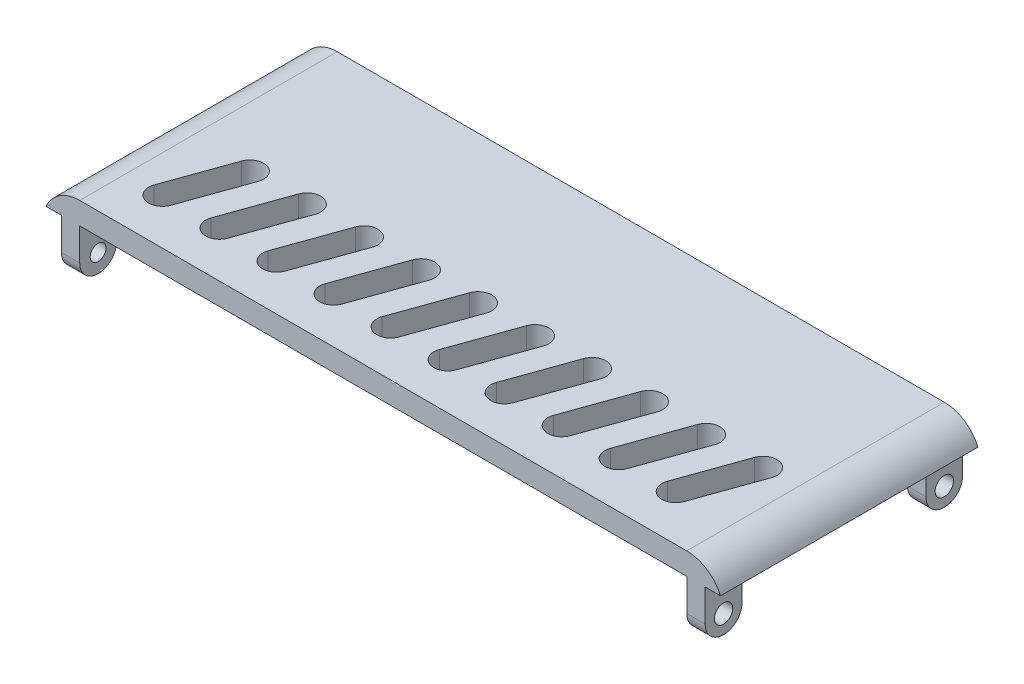
SolidWorks part; units mm, degrees
ref_plane "前视基准面" through (0, 0, 0) normal (0, 0, 1) x (1, 0, 0)
ref_plane "上视基准面" through (0, 0, 0) normal (0, 1, 0) x (1, 0, 0)
ref_plane "右视基准面" through (0, 0, 0) normal (1, 0, 0) x (0, 0, -1)
sketch "草图2" plane through (0, 0, 0) normal (0, 1, 0) x (1, 0, 0)
  line L1 (-31.0872, 15.1404) -> (42.9128, 15.1404)
  line L2 (-31.0872, 15.1404) -> (-31.0872, -12.8596)
  line L3 (-31.0872, -12.8596) -> (42.9128, -12.8596)
  line L4 (42.9128, 15.1404) -> (42.9128, -12.8596)
  dimension "D1" = 74
  dimension "D2" = 28
extrude "凸台-拉伸1" add sketch "草图2" along normal blind 4
fillet "圆角1" radius 4 2 edges at (-31.0872, 4, -1.1404) (42.9128, 4, -1.1404)
sketch "草图3" plane through (0, 0, -15.1404) normal (0, 0, -1) x (-1, 0, 0)
  line L1 (31.0872, 0) -> (-42.9128, 0)
  line L2 (31.0872, 0) -> (31.0872, 1.6)
  line L3 (31.0872, 1.6) -> (-42.9128, 1.6)
  line L4 (-42.9128, 0) -> (-42.9128, 1.6)
  dimension "D1" = 1.6
extrude "切除-拉伸1" cut sketch "草图3" against normal through all
sketch "草图15" plane through (0, 1.6, 0) normal (0, -1, 0) x (1, 0, 0)
  line L0 (33.5789, 9.0596) -> (41.4128, 9.0596)
  line L2 (45.2135, 5.0596) -> (45.2135, 10.0596)
  line L3 (45.2135, 10.0596) -> (33.5789, 10.0596)
  line L4 (33.5789, 9.0596) -> (33.5789, 10.0596)
  line L5 (42.5789, -15.1404) -> (42.5789, 12.8596) construction
  line L6 (41.4128, 9.0596) -> (41.4128, 5.0596)
  line L7 (41.4128, 5.0596) -> (45.2135, 5.0596)
  line L8 (42.9128, 14.8596) -> (42.9128, -17.1404) construction
  line L9 (-30.7532, 12.8596) -> (42.5789, 12.8596) construction
  dimension "D1" = 1
  dimension "D2" = 9
  dimension "D3" = 5
  dimension "D4" = 1.5
  dimension "D5" = 2.8
sketch "草图19" plane through (0, 4, 0) normal (0, 1, 0) x (1, 0, 0)
  line L0 (-20.5872, -0.8596) -> (-23.0872, -7.8596) construction
  line L5 (-19.1746, -1.3641) -> (-21.6746, -8.3641)
  line L8 (-21.9998, -0.3551) -> (-24.4998, -7.3551)
  line L11 (38.9128, 15.1404) -> (-27.0872, 15.1404) construction
  line L14 (-27.0872, -12.8596) -> (38.9128, -12.8596) construction
  line L17 (-14.3872, -0.8596) -> (-16.8872, -7.8596) construction
  line L20 (-12.9746, -1.3641) -> (-15.4746, -8.3641)
  line L23 (-15.7998, -0.3551) -> (-18.2998, -7.3551)
  line L26 (-40.9597, 1.1404) -> (-18.0872, 1.1404) construction
  line L27 (-27.0872, 15.1404) -> (-27.0872, -12.8596) construction
  line L28 (-8.1872, -0.8596) -> (-10.6872, -7.8596) construction
  line L31 (-6.7746, -1.3641) -> (-9.2746, -8.3641)
  line L34 (-9.5998, -0.3551) -> (-12.0998, -7.3551)
  line L37 (-1.9872, -0.8596) -> (-4.4872, -7.8596) construction
  line L40 (-0.5746, -1.3641) -> (-3.0746, -8.3641)
  line L43 (-3.3998, -0.3551) -> (-5.8998, -7.3551)
  line L46 (4.2128, -0.8596) -> (1.7128, -7.8596) construction
  line L49 (5.6254, -1.3641) -> (3.1254, -8.3641)
  line L52 (2.8002, -0.3551) -> (0.3002, -7.3551)
  line L53 (10.4128, -0.8596) -> (7.9128, -7.8596) construction
  line L54 (11.8254, -1.3641) -> (9.3254, -8.3641)
  line L55 (9.0002, -0.3551) -> (6.5002, -7.3551)
  line L56 (16.6128, -0.8596) -> (14.1128, -7.8596) construction
  line L57 (18.0254, -1.3641) -> (15.5254, -8.3641)
  line L58 (15.2002, -0.3551) -> (12.7002, -7.3551)
  line L59 (22.8128, -0.8596) -> (20.3128, -7.8596) construction
  line L60 (24.2254, -1.3641) -> (21.7254, -8.3641)
  line L61 (21.4002, -0.3551) -> (18.9002, -7.3551)
  line L62 (29.0128, -0.8596) -> (26.5128, -7.8596) construction
  line L63 (30.4254, -1.3641) -> (27.9254, -8.3641)
  line L64 (27.6002, -0.3551) -> (25.1002, -7.3551)
  line L65 (35.2128, -0.8596) -> (32.7128, -7.8596) construction
  line L66 (36.6254, -1.3641) -> (34.1254, -8.3641)
  line L67 (33.8002, -0.3551) -> (31.3002, -7.3551)
  arc A32 (-19.1746, -1.3641) -> (-21.9998, -0.3551) centre (-20.5872, -0.8596) ccw
  arc A33 (-24.4998, -7.3551) -> (-21.6746, -8.3641) centre (-23.0872, -7.8596) ccw
  arc A34 (-12.9746, -1.3641) -> (-15.7998, -0.3551) centre (-14.3872, -0.8596) ccw
  arc A35 (-18.2998, -7.3551) -> (-15.4746, -8.3641) centre (-16.8872, -7.8596) ccw
  arc A36 (-6.7746, -1.3641) -> (-9.5998, -0.3551) centre (-8.1872, -0.8596) ccw
  arc A37 (-12.0998, -7.3551) -> (-9.2746, -8.3641) centre (-10.6872, -7.8596) ccw
  arc A38 (-0.5746, -1.3641) -> (-3.3998, -0.3551) centre (-1.9872, -0.8596) ccw
  arc A39 (-5.8998, -7.3551) -> (-3.0746, -8.3641) centre (-4.4872, -7.8596) ccw
  arc A40 (5.6254, -1.3641) -> (2.8002, -0.3551) centre (4.2128, -0.8596) ccw
  arc A41 (0.3002, -7.3551) -> (3.1254, -8.3641) centre (1.7128, -7.8596) ccw
  arc A42 (11.8254, -1.3641) -> (9.0002, -0.3551) centre (10.4128, -0.8596) ccw
  arc A43 (6.5002, -7.3551) -> (9.3254, -8.3641) centre (7.9128, -7.8596) ccw
  arc A44 (18.0254, -1.3641) -> (15.2002, -0.3551) centre (16.6128, -0.8596) ccw
  arc A45 (12.7002, -7.3551) -> (15.5254, -8.3641) centre (14.1128, -7.8596) ccw
  arc A46 (24.2254, -1.3641) -> (21.4002, -0.3551) centre (22.8128, -0.8596) ccw
  arc A47 (18.9002, -7.3551) -> (21.7254, -8.3641) centre (20.3128, -7.8596) ccw
  arc A48 (30.4254, -1.3641) -> (27.6002, -0.3551) centre (29.0128, -0.8596) ccw
  arc A49 (25.1002, -7.3551) -> (27.9254, -8.3641) centre (26.5128, -7.8596) ccw
  arc A50 (36.6254, -1.3641) -> (33.8002, -0.3551) centre (35.2128, -0.8596) ccw
  arc A51 (31.3002, -7.3551) -> (34.1254, -8.3641) centre (32.7128, -7.8596) ccw
  point P2 (-21.8372, -4.3596)
  point P15 (-15.6372, -4.3596)
  point P22 (-9.4372, -4.3596)
  point P29 (-3.2372, -4.3596)
  point P36 (2.9628, -4.3596)
  point P43 (9.1628, -4.3596)
  point P50 (15.3628, -4.3596)
  point P57 (21.5628, -4.3596)
  point P64 (-27.0872, 1.1404)
  point P68 (27.7628, -4.3596)
  point P75 (33.9628, -4.3596)
  dimension "D6" = 4
  dimension "D3" = 1.5
  dimension "D1" = 16
  dimension "D2" = 5
  dimension "D4" = 6.5
  dimension "D5" = 10
extrude "切除-拉伸6" cut sketch "草图19" against normal up to next
sketch "草图21" plane through (0, 1.6, 0) normal (0, -1, 0) x (1, 0, 0)
  line L1 (-22.7532, 12.0596) -> (-12.7532, 12.0596)
  line L2 (-22.7532, 12.0596) -> (-22.7532, 10.0596)
  line L3 (-22.7532, 10.0596) -> (-12.7532, 10.0596)
  line L4 (-12.7532, 12.0596) -> (-12.7532, 10.0596)
  line L5 (30.5789, 10.0596) -> (18.5789, 10.0596)
  line L6 (30.5789, 10.0596) -> (30.5789, 12.0596)
  line L7 (30.5789, 12.0596) -> (18.5789, 12.0596)
  line L8 (18.5789, 10.0596) -> (18.5789, 12.0596)
  line L12 (-30.7532, 12.8596) -> (-30.7532, -15.1404) construction
  point P8 (0, 0)
  dimension "D1" = 2
  dimension "D2" = 8
  dimension "D3" = 10
  dimension "D4" = 12
extrude "凸台-拉伸9" add sketch "草图21" along normal blind 0.15
sketch "草图22" plane through (0, 1.6, 0) normal (0, -1, 0) x (1, 0, 0)
  line L0 (-29.0872, 12.8596) -> (-29.0872, 5.8198) construction
  line L1 (-29.0872, 12.8596) -> (-27.0872, 12.8596)
  line L2 (-29.0872, 12.8596) -> (-29.0872, 8.8596)
  line L3 (-29.0872, 8.8596) -> (-27.0872, 8.8596)
  line L4 (-27.0872, 12.8596) -> (-27.0872, 8.8596)
  line L5 (-29.0872, -1.1802) -> (-29.0872, -15.1404) construction
  line L6 (-29.0872, -11.1404) -> (-27.0872, -11.1404)
  line L7 (-29.0872, -11.1404) -> (-29.0872, -15.1404)
  line L8 (-29.0872, -15.1404) -> (-27.0872, -15.1404)
  line L9 (-27.0872, -11.1404) -> (-27.0872, -15.1404)
  line L10 (-30.7532, -15.1404) -> (42.5789, -15.1404) construction
  line L11 (-30.7532, 12.8596) -> (42.5789, 12.8596) construction
  line L12 (40.9128, -15.1404) -> (40.9128, -1.1802) construction
  line L13 (40.9128, 12.8596) -> (38.9128, 12.8596)
  line L14 (40.9128, 12.8596) -> (40.9128, 8.8596)
  line L15 (40.9128, 8.8596) -> (38.9128, 8.8596)
  line L16 (38.9128, 12.8596) -> (38.9128, 8.8596)
  line L17 (40.9128, -15.1404) -> (38.9128, -15.1404)
  line L18 (40.9128, -15.1404) -> (40.9128, -11.1404)
  line L19 (40.9128, -11.1404) -> (38.9128, -11.1404)
  line L20 (38.9128, -15.1404) -> (38.9128, -11.1404)
  line L21 (40.9128, 5.8198) -> (40.9128, 12.8596) construction
  point P26 (0, 0)
  point P27 (0, 0)
  point P28 (0, 0)
  point P29 (0, 0)
  point P30 (40.9128, -15.1404)
  point P33 (0, 0)
  point P34 (40.9128, 12.8596)
  dimension "D1" = 4
  dimension "D2" = 2
extrude "凸台-拉伸10" add sketch "草图22" along normal blind 5.5
fillet "圆角3" radius 2 8 edges at (-28.0872, -3.9, -15.1404) (-28.0872, -3.9, -11.1404) (-28.0872, -3.9, 8.8596) (-28.0872, -3.9, 12.8596) (39.9128, -3.9, -11.1404) (39.9128, -3.9, -15.1404) (39.9128, -3.9, 12.8596) (39.9128, -3.9, 8.8596)
sketch "草图23" plane through (-29.0872, 0, 0) normal (-1, 0, 0) x (0, 0, 1)
  circle A0 centre (10.8596, -1.9) radius 1
  circle A1 centre (-13.1404, -1.9) radius 1
  dimension "D1" = 2
extrude "切除-拉伸8" cut sketch "草图23" against normal blind 2 draft 4
sketch "草图24" plane through (40.9128, 0, 0) normal (1, 0, 0) x (0, 0, -1)
  circle A0 centre (13.1404, -1.9) radius 1 construction
  circle A1 centre (-10.8596, -1.9) radius 1 construction
  circle A2 centre (13.1404, -1.9) radius 1
  circle A3 centre (-10.8596, -1.9) radius 1
extrude "切除-拉伸9" cut sketch "草图24" against normal blind 2 draft 4
sketch "草图25" plane through (0, 1.6, 0) normal (0, -1, 0) x (1, 0, 0)
  line L1 (-27.0872, 10.0596) -> (-21.0872, 10.0596)
  line L2 (-27.0872, 10.0596) -> (-27.0872, 8.8596)
  line L3 (-27.0872, 8.8596) -> (-21.0872, 8.8596)
  line L4 (-21.0872, 10.0596) -> (-21.0872, 8.8596)
  line L5 (38.9128, 10.0596) -> (34.9128, 10.0596)
  line L6 (38.9128, 10.0596) -> (38.9128, 8.8596)
  line L7 (38.9128, 8.8596) -> (34.9128, 8.8596)
  line L8 (34.9128, 10.0596) -> (34.9128, 8.8596)
  line L10 (38.9128, 10.8596) -> (38.9128, 8.8596) construction
  point P10 (0, 0)
  point P11 (0, 0)
  point P12 (0, 0)
  point P13 (0, 0)
  point P14 (0, 0)
  point P15 (-27.0872, 8.8596)
  point P17 (-27.0872, 9.9994)
  point P18 (-27.0872, 9.9994)
  point P19 (-21.0872, 9.9994)
  point P20 (38.9128, 10.0729)
  point P21 (-27.0872, 9.9994)
  point P22 (0, 0)
  point P23 (0, 0)
  point P25 (0, 0)
  point P26 (0, 0)
  dimension "D1" = 1.2
  dimension "D2" = 6
  dimension "D3" = 4
extrude "凸台-拉伸11" add sketch "草图25" along normal blind 3
chamfer "倒角1" distance 1 angle 33 2 edges at (36.9128, -1.4, 10.0596) (-24.0872, -1.4, 10.0596) first distance on face at (36.9128, 0.1, 10.0596) first distance on face at (-23.6425, 0.55, 10.0596)
